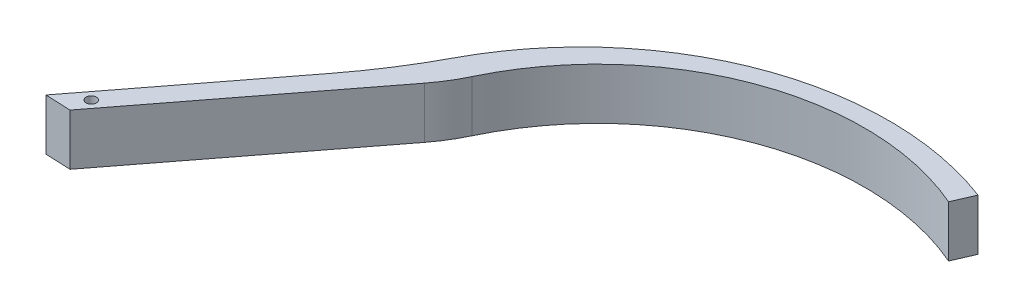
SolidWorks part; units mm, degrees
ref_plane "Front Plane" through (0, 0, 0) normal (0, 0, 1) x (1, 0, 0)
ref_plane "Top Plane" through (0, 0, 0) normal (0, 1, 0) x (1, 0, 0)
ref_plane "Right Plane" through (0, 0, 0) normal (1, 0, 0) x (0, 0, -1)
sketch "Sketch1" plane through (0, 0, 0) normal (0, 1, 0) x (1, 0, 0)
  line L4 (47.7948, 18.9954) -> (48.8939, 21.5354)
  line L5 (0, 0) -> (-19.4955, -25.4)
  line L7 (-19.4955, -25.4) -> (-16.395, -25.5322)
  line L8 (4.122, 1.1987) -> (-16.395, -25.5322)
  arc A1 (4.122, 1.1987) -> (47.7948, 18.9954) centre (34.6814, -11.309) cw
  arc A2 (0, 0) -> (48.8939, 21.5354) centre (35.3973, -14.0939) cw
  circle A3 centre (-16.1587, -23.1399) radius 0.635
  point P5 (49.8973, 19.6098)
  point P10 (11.3789, -5.64)
  point P13 (-14.1712, -38.1)
  point P14 (-6.1345, -42.1548)
  point P15 (53.3406, 16.1435)
  point P16 (55.2527, 30.2011)
  point P17 (-10.5837, -34.1226)
  point P18 (-10.4746, -26.0129)
  point P19 (-11.3761, -8.8755)
  point P20 (0, 0)
  point P21 (-12.2212, -5.5123)
  point P22 (16.6715, -5.5123)
  point P23 (-16.395, -22.9499)
  point P24 (-16.1587, -23.1399)
  dimension "D1" = 33.02
  dimension "D5" = 38.1
  dimension "D6" = 1.27
  dimension "D2" = 2.54
  dimension "D3" = 2.54
  dimension "D4" = 25.4
extrude "Boss-Extrude2" add sketch "Sketch1" along normal blind 6.35
fillet "Fillet3" radius 20.32 1 edges at (4.122, 3.175, -1.1987)
fillet "Fillet4" radius 66.04 1 edges at (0, 3.175, 0)
